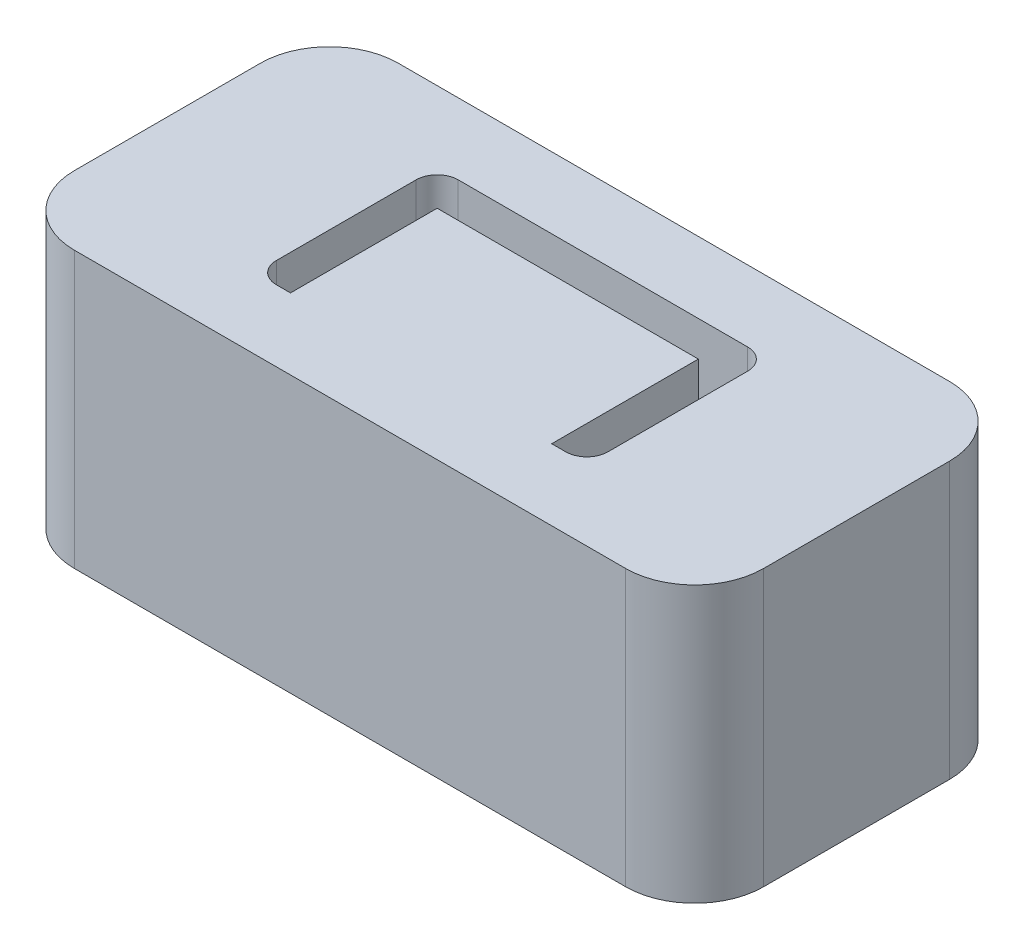
SolidWorks part; units mm, degrees
material "K110"
ref_plane "Front Plane" through (0, 0, 0) normal (0, 0, 1) x (1, 0, 0)
ref_plane "Top Plane" through (0, 0, 0) normal (0, 1, 0) x (1, 0, 0)
ref_plane "Right Plane" through (0, 0, 0) normal (1, 0, 0) x (0, 0, -1)
sketch "Sketch2" plane through (0, 0, 0) normal (0, 1, 0) x (1, 0, 0)
  line L1 (-50, -23.5) -> (50, -23.5)
  line L2 (-50, -23.5) -> (-50, 23.5)
  line L3 (-50, 23.5) -> (50, 23.5)
  line L4 (50, -23.5) -> (50, 23.5)
  line L5 (-50, -23.5) -> (50, 23.5) construction
  line L6 (-50, 23.5) -> (50, -23.5) construction
  point P0 (0, 0)
  dimension "D1" = 100
  dimension "D2" = 47
extrude "Boss-Extrude1" add sketch "Sketch2" against normal blind 40
fillet "Fillet1" radius 10 4 edges at (-50, -20, -23.5) (50, -20, -23.5) (50, -20, 23.5) (-50, -20, 23.5)
sketch "Sketch3" plane through (0, 0, 0) normal (0, 1, 0) x (1, 0, 0)
  line L16 (24.05, -10.14) -> (24.05, 10.14)
  line L17 (18.95, -13.19) -> (21, -13.19)
  line L18 (18.95, 8.09) -> (18.95, -13.19)
  line L19 (-18.95, 8.09) -> (18.95, 8.09)
  line L20 (-18.95, -13.19) -> (-18.95, 8.09)
  line L21 (-21, -13.19) -> (-18.95, -13.19)
  line L22 (-24.05, 10.14) -> (-24.05, -10.14)
  line L23 (21, 13.19) -> (-21, 13.19)
  line L24 (24.05, -10.14) -> (24.05, 10.14)
  line L25 (18.95, -13.19) -> (21, -13.19)
  line L26 (18.95, 8.09) -> (18.95, -13.19)
  line L27 (-18.95, 8.09) -> (18.95, 8.09)
  line L28 (-18.95, -13.19) -> (-18.95, 8.09)
  line L29 (-21, -13.19) -> (-18.95, -13.19)
  line L30 (-24.05, 10.14) -> (-24.05, -10.14)
  line L31 (21, 13.19) -> (-21, 13.19)
  arc A8 (24.05, 10.14) -> (21, 13.19) centre (21, 10.14) ccw
  arc A9 (21, -13.19) -> (24.05, -10.14) centre (21, -10.14) ccw
  arc A10 (-24.05, -10.14) -> (-21, -13.19) centre (-21, -10.14) ccw
  arc A11 (-21, 13.19) -> (-24.05, 10.14) centre (-21, 10.14) ccw
  arc A12 (24.05, 10.14) -> (21, 13.19) centre (21, 10.14) ccw
  arc A13 (21, -13.19) -> (24.05, -10.14) centre (21, -10.14) ccw
  arc A14 (-24.05, -10.14) -> (-21, -13.19) centre (-21, -10.14) ccw
  arc A15 (-21, 13.19) -> (-24.05, 10.14) centre (-21, 10.14) ccw
  dimension "D1" = 0.05
extrude "Cut-Extrude1" cut sketch "Sketch3" against normal up to next
hole_wizard "M6 Tapped Hole1" positions "Sketch6" profile "Sketch5" tap size "M6" standard "ISO"
sketch "Sketch6" plane through (0, -40, 0) normal (0, -1, 0) x (-1, 0, 0)
  line L0 (-50, -13.5) -> (-50, 13.5) construction
  line L1 (-40, 23.5) -> (40, 23.5) construction
  line L2 (40, -23.5) -> (-40, -23.5) construction
  line L3 (50, 13.5) -> (50, -13.5) construction
  point P0 (-43, 16.5)
  point P2 (43, 16.5)
  point P4 (43, -16.5)
  point P6 (-43, -16.5)
  dimension "D1" = 7
  dimension "D2" = 7
  dimension "D3" = 7
  dimension "D4" = 7
sketch "Sketch5" plane through (43, -40, -16.5) normal (1, 0, 0) x (0, 0, -1)
  line L0 (0, 0) -> (0, 18.5022)
  line L1 (0, 18.5022) -> (2.5, 17)
  line L2 (2.5, 17) -> (2.5, 0.525)
  line L3 (2.5, 0.525) -> (3.025, 0)
  line L5 (3.025, 0) -> (0, 0)
  line L6 (-2.5, 0.525) -> (-3.025, 0) construction
  line L10 (0, 18.5022) -> (-2.5, 17) construction
  line L11 (0, -6.35) -> (0, 107.95) construction
  dimension "Tap Drill Dia." = 5
  dimension "Tap Drill Depth" = 17
  dimension "Near C'Sink Dia." = 6.05
  dimension "Near C'Sink Angle" = 90
  dimension "Drill Angle" = 118
cosmetic thread "Hole Thread1"
cosmetic thread "Hole Thread2"
cosmetic thread "Hole Thread3"
cosmetic thread "Hole Thread4"
